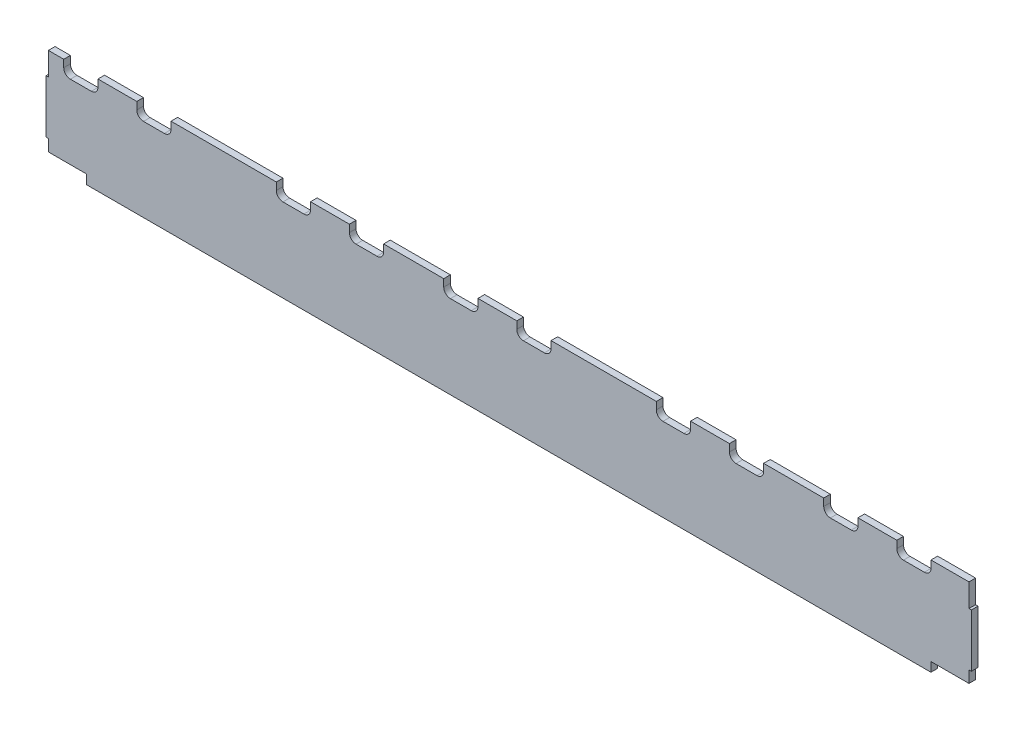
SolidWorks part; units mm, degrees
material "PP Film"
ref_plane "X-Y Datum" through (0, 0, 0) normal (0, 0, 1) x (1, 0, 0)
ref_plane "X-Z Datum" through (0, 0, 0) normal (0, 1, 0) x (1, 0, 0)
ref_plane "Y-Z Datum" through (0, 0, 0) normal (1, 0, 0) x (0, 0, -1)
sketch "Sketch2" plane through (0, 0, 0) normal (0, 0, 1) x (1, 0, 0)
  line L0 (-166.3768, -167.122) -> (-166.3768, -157.216)
  line L1 (-166.3768, -194.808) -> (-166.3768, -199.261)
  line L2 (273.6032, -167.122) -> (273.6032, -157.216)
  line L3 (273.6032, -194.808) -> (273.6032, -199.261)
  line L64 (255.4262, -203.714) -> (255.4262, -199.261)
  line L65 (255.4262, -199.261) -> (275.7462, -199.261)
  line L66 (275.7462, -199.261) -> (275.7462, -194.808)
  line L67 (275.7462, -194.808) -> (273.6032, -194.808)
  line L68 (273.6032, -194.808) -> (273.6032, -193.665)
  line L69 (273.6032, -193.665) -> (274.7462, -193.665)
  line L70 (274.7462, -193.665) -> (274.7462, -168.265)
  line L71 (274.7462, -168.265) -> (273.6032, -168.265)
  line L72 (273.6032, -168.265) -> (273.6032, -167.122)
  line L73 (273.6032, -167.122) -> (275.7462, -167.122)
  line L74 (275.7462, -167.122) -> (275.7462, -157.216)
  line L75 (275.7462, -157.216) -> (255.4633, -157.216)
  line L76 (255.4633, -157.216) -> (255.4633, -160.708)
  line L77 (252.2883, -163.883) -> (242.2883, -163.883)
  line L78 (239.1133, -160.708) -> (239.1133, -157.216)
  line L79 (239.1133, -157.216) -> (220.5383, -157.216)
  line L80 (220.5383, -157.216) -> (220.5383, -160.708)
  line L81 (217.3633, -163.883) -> (207.3633, -163.883)
  line L82 (204.1883, -160.708) -> (204.1883, -157.216)
  line L83 (204.1883, -157.216) -> (175.4521, -157.216)
  line L84 (175.4521, -157.216) -> (175.4521, -160.708)
  line L85 (172.2771, -163.883) -> (162.2771, -163.883)
  line L86 (159.1021, -160.708) -> (159.1021, -157.216)
  line L87 (159.1021, -157.216) -> (140.5271, -157.216)
  line L88 (140.5271, -157.216) -> (140.5271, -160.708)
  line L89 (137.3521, -163.883) -> (127.3521, -163.883)
  line L90 (124.1771, -160.708) -> (124.1771, -157.216)
  line L91 (124.1771, -157.216) -> (73.8493, -157.216)
  line L92 (73.8493, -157.216) -> (73.8493, -160.708)
  line L93 (70.6743, -163.883) -> (60.6743, -163.883)
  line L94 (57.4993, -160.708) -> (57.4993, -157.216)
  line L95 (57.4993, -157.216) -> (38.9243, -157.216)
  line L96 (38.9243, -157.216) -> (38.9243, -160.708)
  line L97 (35.7493, -163.883) -> (25.7493, -163.883)
  line L98 (22.5743, -160.708) -> (22.5743, -157.216)
  line L99 (22.5743, -157.216) -> (-6.1619, -157.216)
  line L100 (-6.1619, -157.216) -> (-6.1619, -160.708)
  line L101 (-9.3369, -163.883) -> (-19.3369, -163.883)
  line L102 (-22.5119, -160.708) -> (-22.5119, -157.216)
  line L103 (-22.5119, -157.216) -> (-41.0869, -157.216)
  line L104 (-41.0869, -157.216) -> (-41.0869, -160.708)
  line L105 (-44.2619, -163.883) -> (-54.2619, -163.883)
  line L106 (-57.4369, -160.708) -> (-57.4369, -157.216)
  line L107 (-57.4369, -157.216) -> (-107.7647, -157.216)
  line L108 (-107.7647, -157.216) -> (-107.7647, -160.708)
  line L109 (-110.9397, -163.883) -> (-120.9397, -163.883)
  line L110 (-124.1147, -160.708) -> (-124.1147, -157.216)
  line L111 (-124.1147, -157.216) -> (-142.6897, -157.216)
  line L112 (-142.6897, -157.216) -> (-142.6897, -160.708)
  line L113 (-145.8647, -163.883) -> (-155.8647, -163.883)
  line L114 (-159.0397, -160.708) -> (-159.0397, -157.216)
  line L115 (-159.0397, -157.216) -> (-168.5198, -157.216)
  line L116 (-168.5198, -157.216) -> (-168.5198, -167.122)
  line L117 (-168.5198, -167.122) -> (-166.3768, -167.122)
  line L118 (-166.3768, -167.122) -> (-166.3768, -168.265)
  line L119 (-166.3768, -168.265) -> (-167.5198, -168.265)
  line L120 (-167.5198, -168.265) -> (-167.5198, -193.665)
  line L121 (-167.5198, -193.665) -> (-166.3768, -193.665)
  line L122 (-166.3768, -193.665) -> (-166.3768, -194.808)
  line L123 (-166.3768, -194.808) -> (-168.5198, -194.808)
  line L124 (-168.5198, -194.808) -> (-168.5198, -199.261)
  line L125 (-168.5198, -199.261) -> (-148.1998, -199.261)
  line L126 (-148.1998, -199.261) -> (-148.1998, -203.714)
  line L127 (-148.1998, -203.714) -> (255.4262, -203.714)
  line L128 (255.4262, -203.714) -> (255.4262, -199.261)
  line L129 (255.4262, -199.261) -> (275.7462, -199.261)
  line L130 (275.7462, -199.261) -> (275.7462, -194.808)
  line L131 (275.7462, -194.808) -> (273.6032, -194.808)
  line L132 (273.6032, -194.808) -> (273.6032, -193.665)
  line L133 (273.6032, -193.665) -> (274.7462, -193.665)
  line L134 (274.7462, -193.665) -> (274.7462, -168.265)
  line L135 (274.7462, -168.265) -> (273.6032, -168.265)
  line L136 (273.6032, -168.265) -> (273.6032, -167.122)
  line L137 (273.6032, -167.122) -> (275.7462, -167.122)
  line L138 (275.7462, -167.122) -> (275.7462, -157.216)
  line L139 (275.7462, -157.216) -> (255.4633, -157.216)
  line L140 (255.4633, -157.216) -> (255.4633, -160.708)
  line L141 (252.2883, -163.883) -> (242.2883, -163.883)
  line L142 (239.1133, -160.708) -> (239.1133, -157.216)
  line L143 (239.1133, -157.216) -> (220.5383, -157.216)
  line L144 (220.5383, -157.216) -> (220.5383, -160.708)
  line L145 (217.3633, -163.883) -> (207.3633, -163.883)
  line L146 (204.1883, -160.708) -> (204.1883, -157.216)
  line L147 (204.1883, -157.216) -> (175.4521, -157.216)
  line L148 (175.4521, -157.216) -> (175.4521, -160.708)
  line L149 (172.2771, -163.883) -> (162.2771, -163.883)
  line L150 (159.1021, -160.708) -> (159.1021, -157.216)
  line L151 (159.1021, -157.216) -> (140.5271, -157.216)
  line L152 (140.5271, -157.216) -> (140.5271, -160.708)
  line L153 (137.3521, -163.883) -> (127.3521, -163.883)
  line L154 (124.1771, -160.708) -> (124.1771, -157.216)
  line L155 (124.1771, -157.216) -> (73.8493, -157.216)
  line L156 (73.8493, -157.216) -> (73.8493, -160.708)
  line L157 (70.6743, -163.883) -> (60.6743, -163.883)
  line L158 (57.4993, -160.708) -> (57.4993, -157.216)
  line L159 (57.4993, -157.216) -> (38.9243, -157.216)
  line L160 (38.9243, -157.216) -> (38.9243, -160.708)
  line L161 (35.7493, -163.883) -> (25.7493, -163.883)
  line L162 (22.5743, -160.708) -> (22.5743, -157.216)
  line L163 (22.5743, -157.216) -> (-6.1619, -157.216)
  line L164 (-6.1619, -157.216) -> (-6.1619, -160.708)
  line L165 (-9.3369, -163.883) -> (-19.3369, -163.883)
  line L166 (-22.5119, -160.708) -> (-22.5119, -157.216)
  line L167 (-22.5119, -157.216) -> (-41.0869, -157.216)
  line L168 (-41.0869, -157.216) -> (-41.0869, -160.708)
  line L169 (-44.2619, -163.883) -> (-54.2619, -163.883)
  line L170 (-57.4369, -160.708) -> (-57.4369, -157.216)
  line L171 (-57.4369, -157.216) -> (-107.7647, -157.216)
  line L172 (-107.7647, -157.216) -> (-107.7647, -160.708)
  line L173 (-110.9397, -163.883) -> (-120.9397, -163.883)
  line L174 (-124.1147, -160.708) -> (-124.1147, -157.216)
  line L175 (-124.1147, -157.216) -> (-142.6897, -157.216)
  line L176 (-142.6897, -157.216) -> (-142.6897, -160.708)
  line L177 (-145.8647, -163.883) -> (-155.8647, -163.883)
  line L178 (-159.0397, -160.708) -> (-159.0397, -157.216)
  line L179 (-159.0397, -157.216) -> (-168.5198, -157.216)
  line L180 (-168.5198, -157.216) -> (-168.5198, -167.122)
  line L181 (-168.5198, -167.122) -> (-166.3768, -167.122)
  line L182 (-166.3768, -167.122) -> (-166.3768, -168.265)
  line L183 (-166.3768, -168.265) -> (-167.5198, -168.265)
  line L184 (-167.5198, -168.265) -> (-167.5198, -193.665)
  line L185 (-167.5198, -193.665) -> (-166.3768, -193.665)
  line L186 (-166.3768, -193.665) -> (-166.3768, -194.808)
  line L187 (-166.3768, -194.808) -> (-168.5198, -194.808)
  line L188 (-168.5198, -194.808) -> (-168.5198, -199.261)
  line L189 (-168.5198, -199.261) -> (-148.1998, -199.261)
  line L190 (-148.1998, -199.261) -> (-148.1998, -203.714)
  line L191 (-148.1998, -203.714) -> (255.4262, -203.714)
  arc A20 (252.2883, -163.883) -> (255.4633, -160.708) centre (252.2883, -160.708) ccw
  arc A21 (239.1133, -160.708) -> (242.2883, -163.883) centre (242.2883, -160.708) ccw
  arc A22 (217.3633, -163.883) -> (220.5383, -160.708) centre (217.3633, -160.708) ccw
  arc A23 (204.1883, -160.708) -> (207.3633, -163.883) centre (207.3633, -160.708) ccw
  arc A24 (172.2771, -163.883) -> (175.4521, -160.708) centre (172.2771, -160.708) ccw
  arc A25 (159.1021, -160.708) -> (162.2771, -163.883) centre (162.2771, -160.708) ccw
  arc A26 (137.3521, -163.883) -> (140.5271, -160.708) centre (137.3521, -160.708) ccw
  arc A27 (124.1771, -160.708) -> (127.3521, -163.883) centre (127.3521, -160.708) ccw
  arc A28 (70.6743, -163.883) -> (73.8493, -160.708) centre (70.6743, -160.708) ccw
  arc A29 (57.4993, -160.708) -> (60.6743, -163.883) centre (60.6743, -160.708) ccw
  arc A30 (35.7493, -163.883) -> (38.9243, -160.708) centre (35.7493, -160.708) ccw
  arc A31 (22.5743, -160.708) -> (25.7493, -163.883) centre (25.7493, -160.708) ccw
  arc A32 (-9.3369, -163.883) -> (-6.1619, -160.708) centre (-9.3369, -160.708) ccw
  arc A33 (-22.5119, -160.708) -> (-19.3369, -163.883) centre (-19.3369, -160.708) ccw
  arc A34 (-44.2619, -163.883) -> (-41.0869, -160.708) centre (-44.2619, -160.708) ccw
  arc A35 (-57.4369, -160.708) -> (-54.2619, -163.883) centre (-54.2619, -160.708) ccw
  arc A36 (-110.9397, -163.883) -> (-107.7647, -160.708) centre (-110.9397, -160.708) ccw
  arc A37 (-124.1147, -160.708) -> (-120.9397, -163.883) centre (-120.9397, -160.708) ccw
  arc A38 (-145.8647, -163.883) -> (-142.6897, -160.708) centre (-145.8647, -160.708) ccw
  arc A39 (-159.0397, -160.708) -> (-155.8647, -163.883) centre (-155.8647, -160.708) ccw
  arc A40 (252.2883, -163.883) -> (255.4633, -160.708) centre (252.2883, -160.708) ccw
  arc A41 (239.1133, -160.708) -> (242.2883, -163.883) centre (242.2883, -160.708) ccw
  arc A42 (217.3633, -163.883) -> (220.5383, -160.708) centre (217.3633, -160.708) ccw
  arc A43 (204.1883, -160.708) -> (207.3633, -163.883) centre (207.3633, -160.708) ccw
  arc A44 (172.2771, -163.883) -> (175.4521, -160.708) centre (172.2771, -160.708) ccw
  arc A45 (159.1021, -160.708) -> (162.2771, -163.883) centre (162.2771, -160.708) ccw
  arc A46 (137.3521, -163.883) -> (140.5271, -160.708) centre (137.3521, -160.708) ccw
  arc A47 (124.1771, -160.708) -> (127.3521, -163.883) centre (127.3521, -160.708) ccw
  arc A48 (70.6743, -163.883) -> (73.8493, -160.708) centre (70.6743, -160.708) ccw
  arc A49 (57.4993, -160.708) -> (60.6743, -163.883) centre (60.6743, -160.708) ccw
  arc A50 (35.7493, -163.883) -> (38.9243, -160.708) centre (35.7493, -160.708) ccw
  arc A51 (22.5743, -160.708) -> (25.7493, -163.883) centre (25.7493, -160.708) ccw
  arc A52 (-9.3369, -163.883) -> (-6.1619, -160.708) centre (-9.3369, -160.708) ccw
  arc A53 (-22.5119, -160.708) -> (-19.3369, -163.883) centre (-19.3369, -160.708) ccw
  arc A54 (-44.2619, -163.883) -> (-41.0869, -160.708) centre (-44.2619, -160.708) ccw
  arc A55 (-57.4369, -160.708) -> (-54.2619, -163.883) centre (-54.2619, -160.708) ccw
  arc A56 (-110.9397, -163.883) -> (-107.7647, -160.708) centre (-110.9397, -160.708) ccw
  arc A57 (-124.1147, -160.708) -> (-120.9397, -163.883) centre (-120.9397, -160.708) ccw
  arc A58 (-145.8647, -163.883) -> (-142.6897, -160.708) centre (-145.8647, -160.708) ccw
  arc A59 (-159.0397, -160.708) -> (-155.8647, -163.883) centre (-155.8647, -160.708) ccw
  dimension "D1" = 0
extrude "Boss-Extrude1" add sketch "Sketch2" along normal blind 3.175 contours A59 L178 L179 L0 L182 L183 L184 L185 L186 L1 L189 L190 L191 L128 L129 L3 L132 L133 L134 L135 L136 L2 L139 L140 A40 L141 A41 L142 L143 L144 A42 L145 A43 L146 L147 L148 A44 L149 A45 L150 L151 L152 A46 L153 A47 L154 L155 L156 A48 L157 A49 region at (53.6719, -181.3759, 0)
